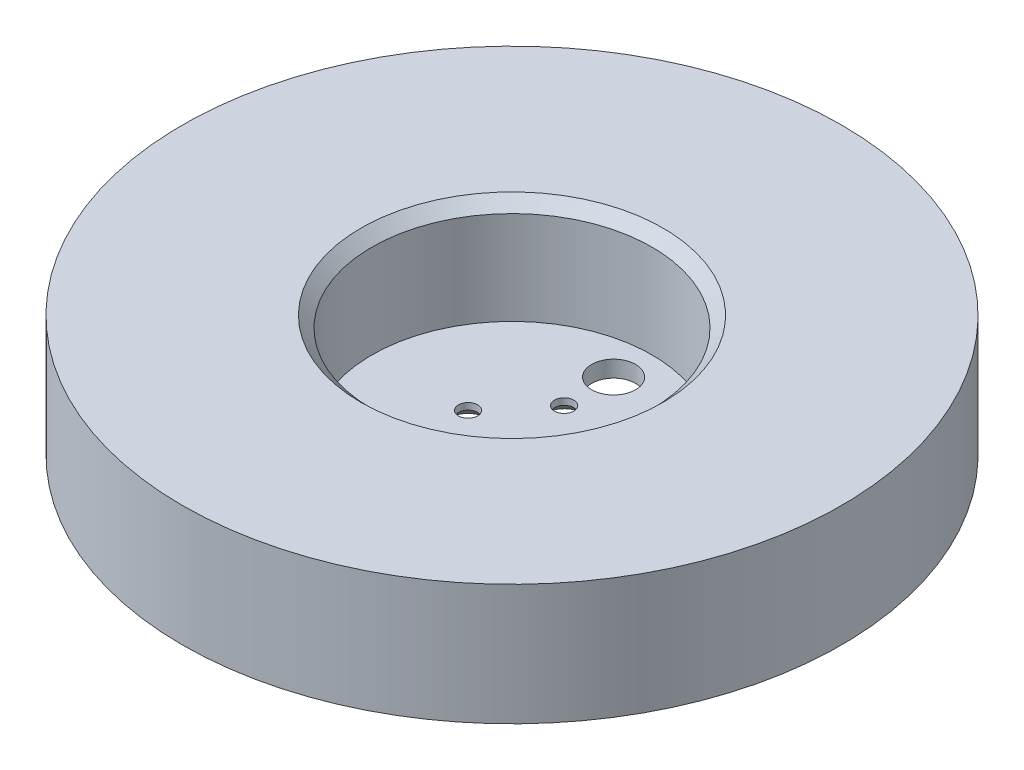
SolidWorks part; units mm, degrees
ref_plane "Front Plane" through (0, 0, 0) normal (0, 0, 1) x (1, 0, 0)
ref_plane "Top Plane" through (0, 0, 0) normal (0, 1, 0) x (1, 0, 0)
ref_plane "Right Plane" through (0, 0, 0) normal (1, 0, 0) x (0, 0, -1)
sketch "Sketch1" plane through (0, 0, 0) normal (0, 1, 0) x (1, 0, 0)
  circle A0 centre (0, 0) radius 60
  dimension "D1" = 120
extrude "Boss-Extrude1" add sketch "Sketch1" along normal blind 3
sketch "Sketch2" plane through (0, 3, 0) normal (0, 1, 0) x (1, 0, 0)
  circle A0 centre (0, 0) radius 25.5
  circle A2 centre (0, 0) radius 60
  circle A3 centre (0, 0) radius 60
  dimension "D1" = 0
  dimension "D2" = 51
extrude "Boss-Extrude2" add sketch "Sketch2" along normal blind 19
sketch "Sketch3" plane through (0, 0, 0) normal (0, -1, 0) x (1, 0, 0)
  circle A0 centre (0, 0) radius 52.5
  circle A1 centre (0, 0) radius 42.5
  dimension "D1" = 85
  dimension "D2" = 10
extrude "Cut-Extrude1" cut sketch "Sketch3" against normal blind 10
sketch "Sketch4" plane through (0, 3, 0) normal (0, 1, 0) x (1, 0, 0)
  circle A0 centre (0, 0) radius 9.5 construction
  circle A1 centre (0, 0) radius 8 construction
  circle A2 centre (0, 9.5) radius 1.75
  circle A4 centre (0, -9.5) radius 1.75
  circle A5 centre (-8, 0) radius 1.75
  circle A6 centre (8, 0) radius 1.75
  dimension "D1" = 19
  dimension "D2" = 3.5
  dimension "D3" = 16
extrude "Cut-Extrude2" cut sketch "Sketch4" against normal through all
chamfer "Chamfer1" distance 2 angle 45 1 edges at (0, 22, 25.5)
chamfer "Chamfer2" distance 1.8 angle 45 4 edges at (0, 0, -7.75) (-8, 0, 1.75) (8, 0, 1.75) (0, 0, 11.25)
sketch "Sketch5" plane through (0, 3, 0) normal (0, 1, 0) x (1, 0, 0)
  line L0 (0, 18.5) -> (0, 0) construction
  circle A0 centre (0, 0) radius 12.5 construction
  circle A1 centre (0, 18.5) radius 4
  dimension "D1" = 25
  dimension "D2" = 8
  dimension "D3" = 18.5
extrude "Cut-Extrude3" cut sketch "Sketch5" against normal through all
sketch "Sketch6" plane through (0, 0, 0) normal (0, -1, 0) x (1, 0, 0)
  line L0 (0, 0) -> (0, 42.5) construction
  circle A0 centre (0, 42.5) radius 5
  circle A1 centre (0, 0) radius 42.5 construction
  dimension "D1" = 10
extrude "Cut-Extrude4" cut sketch "Sketch6" against normal up to surface (10 mm away) up to face at (0, 10, -42.5)
sketch "Sketch8" plane through (0, 0, 0) normal (0, -1, 0) x (1, 0, 0)
  line L0 (50.1164, 0.2371) -> (50.1164, -0.2371)
  line L1 (54.6215, 2.2221) -> (42.4649, 1.7275)
  line L2 (54.6199, -2.2613) -> (42.4636, -1.758)
  arc A0 (53.2877, -2.2062) -> (53.2893, 2.1679) centre (0, 0) ccw construction
  arc A1 (54.6428, 1.6139) -> (54.6215, 2.2221) centre (0, 0) ccw
  arc A2 (50.074, -2.0731) -> (50.0755, 2.0371) centre (0, 0) ccw construction
  arc A3 (51.6224, -2.1372) -> (51.624, 2.1001) centre (0, 0) ccw construction
  arc A5 (42.4636, -1.758) -> (42.4649, 1.7275) centre (0, 0) ccw
  arc A6 (-4.9913, 42.2059) -> (4.9913, 42.2059) centre (0, 0) ccw construction
  arc A7 (54.6199, -2.2613) -> (54.6428, -1.6139) centre (0, 0) ccw
  spline S0 degree 4 poles (50.1164, 0.2371) (50.1234, 0.2372) (50.1431, 0.2377) (50.1804, 0.2393) (50.2413, 0.2432) (50.3188, 0.2498) (50.419, 0.2603) (50.537, 0.2751) (50.6668, 0.2939) (50.8079, 0.3171) (50.9488, 0.3427) (51.0893, 0.3706) (51.2292, 0.4004) (51.3988, 0.439) (51.6021, 0.4886) (51.8397, 0.5516) (52.1092, 0.6289) (52.3839, 0.714) (52.6541, 0.8029) (52.9272, 0.8987) (53.1914, 0.9956) (53.4659, 1.1024) (53.7192, 1.204) (54.003, 1.3248) (54.2321, 1.4242) (54.5343, 1.5626) (54.7128, 1.6465) (54.9217, 1.7472) (55.0144, 1.7932) (55.0715, 1.8216) knots 0 0 0 0 0 0.005377 0.015084 0.028532 0.04661 0.064855 0.092111 0.119476 0.146842 0.174209 0.201575 0.228941 0.256307 0.307035 0.361767 0.4165 0.471232 0.525964 0.580697 0.635429 0.690161 0.744894 0.799626 0.854358 0.909091 0.954545 1 1 1 1 1 construction
  spline S1 degree 4 poles (50.1164, 0.2371) (50.1234, 0.2372) (50.1431, 0.2377) (50.1804, 0.2393) (50.2413, 0.2432) (50.3188, 0.2498) (50.419, 0.2603) (50.537, 0.2751) (50.6668, 0.2939) (50.8079, 0.3171) (50.9488, 0.3427) (51.0893, 0.3706) (51.2292, 0.4004) (51.3988, 0.439) (51.6021, 0.4886) (51.8397, 0.5516) (52.1092, 0.6289) (52.3839, 0.714) (52.6541, 0.8029) (52.9272, 0.8987) (53.1914, 0.9956) (53.4659, 1.1024) (53.7192, 1.204) (54.003, 1.3248) (54.2321, 1.4242) (54.4688, 1.5326) (54.584, 1.5861) (54.6428, 1.6139) knots 0 0 0 0 0 0.005377 0.015084 0.028532 0.04661 0.064855 0.092111 0.119476 0.146842 0.174209 0.201575 0.228941 0.256307 0.307035 0.361767 0.4165 0.471232 0.525964 0.580697 0.635429 0.690161 0.744894 0.799626 0.854358 0.909091 0.909091 0.909091 0.909091 0.909091
  spline S2 degree 4 poles (50.1164, -0.2371) (50.1234, -0.2372) (50.1431, -0.2377) (50.1804, -0.2393) (50.2413, -0.2432) (50.3188, -0.2498) (50.419, -0.2603) (50.537, -0.2751) (50.6668, -0.2939) (50.8079, -0.3171) (50.9488, -0.3427) (51.0893, -0.3706) (51.2292, -0.4004) (51.3988, -0.439) (51.6021, -0.4886) (51.8397, -0.5516) (52.1092, -0.6289) (52.3839, -0.714) (52.6541, -0.8029) (52.9272, -0.8987) (53.1914, -0.9956) (53.4659, -1.1024) (53.7192, -1.204) (54.003, -1.3248) (54.2321, -1.4242) (54.5343, -1.5626) (54.7128, -1.6465) (54.9217, -1.7472) (55.0144, -1.7932) (55.0715, -1.8216) knots 0 0 0 0 0 0.005377 0.015084 0.028532 0.04661 0.064855 0.092111 0.119476 0.146842 0.174209 0.201575 0.228941 0.256307 0.307035 0.361767 0.4165 0.471232 0.525964 0.580697 0.635429 0.690161 0.744894 0.799626 0.854358 0.909091 0.954545 1 1 1 1 1 construction
  spline S3 degree 4 poles (50.1164, -0.2371) (50.1234, -0.2372) (50.1431, -0.2377) (50.1804, -0.2393) (50.2413, -0.2432) (50.3188, -0.2498) (50.419, -0.2603) (50.537, -0.2751) (50.6668, -0.2939) (50.8079, -0.3171) (50.9488, -0.3427) (51.0893, -0.3706) (51.2292, -0.4004) (51.3988, -0.439) (51.6021, -0.4886) (51.8397, -0.5516) (52.1092, -0.6289) (52.3839, -0.714) (52.6541, -0.8029) (52.9272, -0.8987) (53.1914, -0.9956) (53.4659, -1.1024) (53.7192, -1.204) (54.003, -1.3248) (54.2321, -1.4242) (54.4688, -1.5326) (54.584, -1.5861) (54.6428, -1.6139) knots 0 0 0 0 0 0.005377 0.015084 0.028532 0.04661 0.064855 0.092111 0.119476 0.146842 0.174209 0.201575 0.228941 0.256307 0.307035 0.361767 0.4165 0.471232 0.525964 0.580697 0.635429 0.690161 0.744894 0.799626 0.854358 0.909091 0.909091 0.909091 0.909091 0.909091
  point P3 (54.6428, -2.2613)
  point P21 (54.6428, -3.1441)
  point P22 (54.6428, 3.9479)
  point P23 (54.6428, -2.6816)
  point P24 (54.6428, 2.2221)
  arc M10 (-4.9913, 42.2059) -> (4.9913, 42.2059) centre (0, 0) ccw
  dimension "D2" = 103.3333
  dimension "D3" = 106.6667
  dimension "D4" = 100.2339
extrude "Cut-Extrude5" cut sketch "Sketch8" against normal up to surface (10 mm away) contours L0 S3 S1 | S3 L0 S1 A1 A5 M10 region at (48.0919, 0, -0.0205) up to face at (0, 10, -2.5)
fillet "Fillet1" radius 0.4473 2 edges at (54.6428, 5, 1.6139) (54.6428, 5, -1.6139)
pattern_circular "CirPattern2" count 80 every 4.5 about axis through (0, 3, 0) along (0, -1, 0) of "Fillet1", "Cut-Extrude5"
equation "\"DiametralPitch\"= 0.75"
equation "\"NumTeeth\"= 80"
equation "\"PressureAngle\"= 20deg"
equation "\"Addendum\"= 1 / \"DiametralPitch\""
equation "\"Dedendum\"= 1.25 / \"DiametralPitch\""
equation "\"WorkingDepth\"= 2 / \"DiametralPitch\""
equation "\"WholeDepth\"= 2.25 / \"DiametralPitch\""
equation "\"Clearance\"= 0.25 / \"DiametralPitch\""
equation "\"ToothThickness\"= 1.5708 / \"DiametralPitch\""
equation "\"CircularPitch\"= pi / \"DiametralPitch\""
equation "\"PitchCircle\"= \"NumTeeth\" / \"DiametralPitch\""
equation "\"OutsideDiameter\"= ( \"NumTeeth\" + 2 ) / \"DiametralPitch\""
equation "\"Fillet\"= \"Clearance\" * cos ( \"PressureAngle\" ) * tan ( ( 90 + \"PressureAngle\" ) / 2 )"
equation "\"AddendumCircle\"= \"PitchCircle\" + ( 2 * \"Addendum\" )"
equation "\"DedendumCircle\"= \"PitchCircle\" - ( 2 * \"Dedendum\" )"
equation "\"BaseCircle\"= \"PitchCircle\" * cos ( \"PressureAngle\" )"
equation "\"PitchAngle\"= 360deg / \"NumTeeth\""
equation "\"Alpha\"= sqr ( \"PitchCircle\" ^ 2 - \"BaseCircle\" ^ 2 ) / \"BaseCircle\" * 180 / PI - \"PressureAngle\""
equation "\"Beta\"= ( \"PitchAngle\" / 4 - \"Alpha\" )"
equation "\"Phi\"= sqr ( ( \"AddendumCircle\" / 2 ) ^ 2 - ( \"BaseCircle\" / 2 ) ^ 2 ) / ( \"BaseCircle\" / 2 )"
equation "\"D2@Sketch8\"=\"DedendumCircle\""
equation "\"D3@Sketch8\"=\"PitchCircle\""
equation "\"D4@Sketch8\"=\"BaseCircle\""
equation "\"D1@Fillet1\"=\"Fillet\""
equation "\"D2@CirPattern2\"=\"PitchAngle\""
equation "\"D1@CirPattern2\"=\"NumTeeth\""
